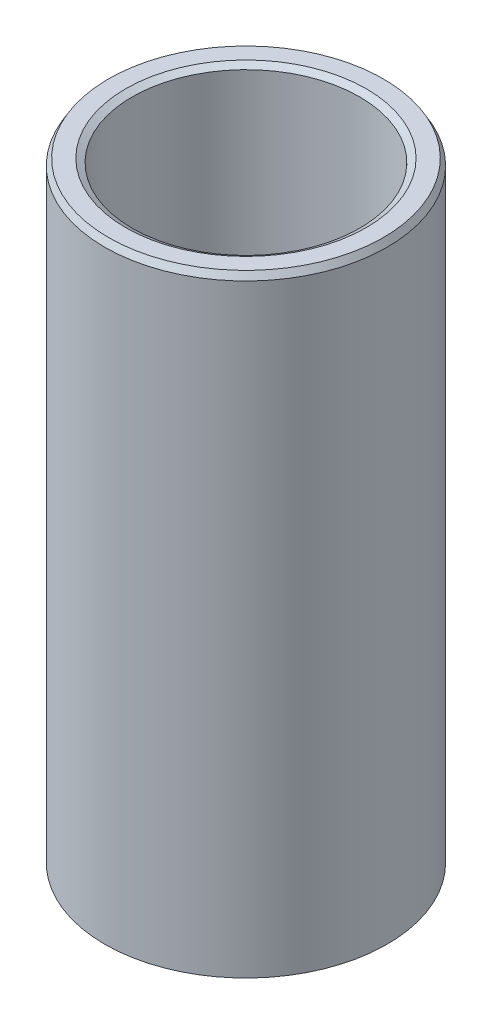
SolidWorks part; units mm, degrees
ref_plane "Front Plane" through (0, 0, 0) normal (0, 0, 1) x (1, 0, 0)
ref_plane "Top Plane" through (0, 0, 0) normal (0, 1, 0) x (1, 0, 0)
ref_plane "Right Plane" through (0, 0, 0) normal (1, 0, 0) x (0, 0, -1)
sketch "Sketch1" plane through (0, 0, 0) normal (0, 1, 0) x (1, 0, 0)
  circle A0 centre (0, 0) radius 45
  dimension "SLEEVE_OD" = 90
extrude "Boss-Extrude1" add sketch "Sketch1" along normal blind 195.673
sketch "Sketch2" plane through (0, 0, 0) normal (0, 1, 0) x (1, 0, 0)
  circle A0 centre (0, 0) radius 36.2648
  dimension "BORE_D" = 72.5296
extrude "Cut-Extrude1" cut sketch "Sketch2" along normal through all
chamfer "Chamfer1" distance 2.0786 angle 30 4 edges at (0, 195.673, 36.2648) (0, 0, 36.2648) (0, 0, 45) (0, 195.673, 45) first distance on face at (0, 195.673, 36.2648) first distance on face at (0, 0, 36.2648) first distance on face at (0, 195.673, 45)
